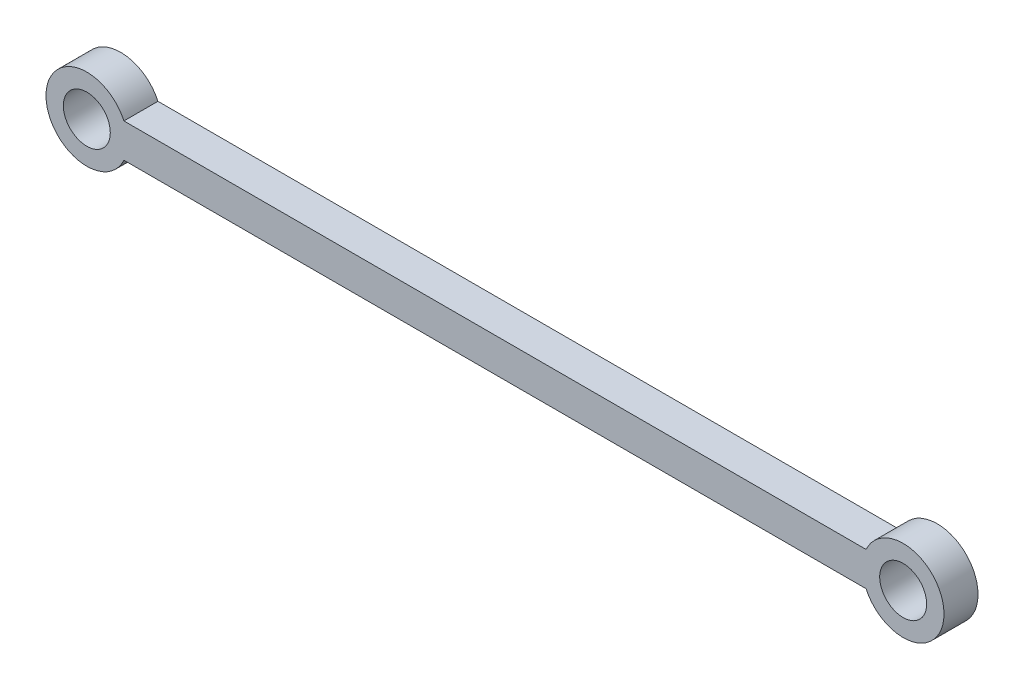
SolidWorks part; units mm, degrees
note: The reader was unsure of these and kept them because the rebuilt part matched: thickness of "Base-Flange1", "Sheet-Metal1".
ref_plane "Front Plane" through (0, 0, 0) normal (0, 0, 1) x (1, 0, 0)
ref_plane "Top Plane" through (0, 0, 0) normal (0, 1, 0) x (1, 0, 0)
ref_plane "Right Plane" through (0, 0, 0) normal (1, 0, 0) x (0, 0, -1)
sketch "Sketch1" plane through (0, 0, 0) normal (0, 0, 1) x (1, 0, 0)
  line L1 (-114.5456, 2.5) -> (-5.4544, 2.5)
  line L2 (-114.5456, 2.5) -> (-114.5456, -2.5) construction
  line L3 (-114.5456, -2.5) -> (-5.4544, -2.5)
  line L4 (-5.4544, 2.5) -> (-5.4544, -2.5) construction
  circle A0 centre (0, 0) radius 3.45
  arc A1 (-114.5456, 2.5) -> (-114.5456, -2.5) centre (-120, 0) ccw
  circle A2 centre (-120, 0) radius 3.45
  arc A3 (-5.4544, -2.5) -> (-5.4544, 2.5) centre (0, 0) ccw
  arc A4 (-114.5456, -2.5) -> (-114.5456, 2.5) centre (-120, 0) ccw construction
  arc A5 (-5.4544, 2.5) -> (-5.4544, -2.5) centre (0, 0) ccw construction
  dimension "D1" = 6.9
  dimension "D2" = 12
  dimension "D3" = 120
  dimension "D4" = 5
base flange "Base-Flange1" sketch "Sketch1" thickness 5 reverse thickness direction no parameters "D1"=0.7366
sketch "Bend-Lines1" [suppressed] plane through (0, 0, 0) normal (0, 1, 0) x (1, 0, 0)
sketch "Bounding-Box1" [suppressed] plane through (0, 0, 0) normal (0, 1, 0) x (1, 0, 0)
sheet metal parameters "Sheet-Metal1" thickness 5 parameters "D1"=0.7366
flat pattern "Flat-Pattern1" [suppressed]
sketch "Bend-Lines2" plane through (0, 0, 0) normal (0, 1, 0) x (1, 0, 0)
sketch3d "Bounding-Box2" [suppressed]
  line L0 (-5.9999, -5.9998, 0) -> (125.9999, -5.9998, 0) construction
  line L1 (-5.9999, 6, 0) -> (125.9999, 6, 0) construction
  line L2 (-5.9999, -5.9998, 0) -> (-5.9999, 6, 0) construction
  line L3 (125.9999, -5.9998, 0) -> (125.9999, 6, 0) construction
